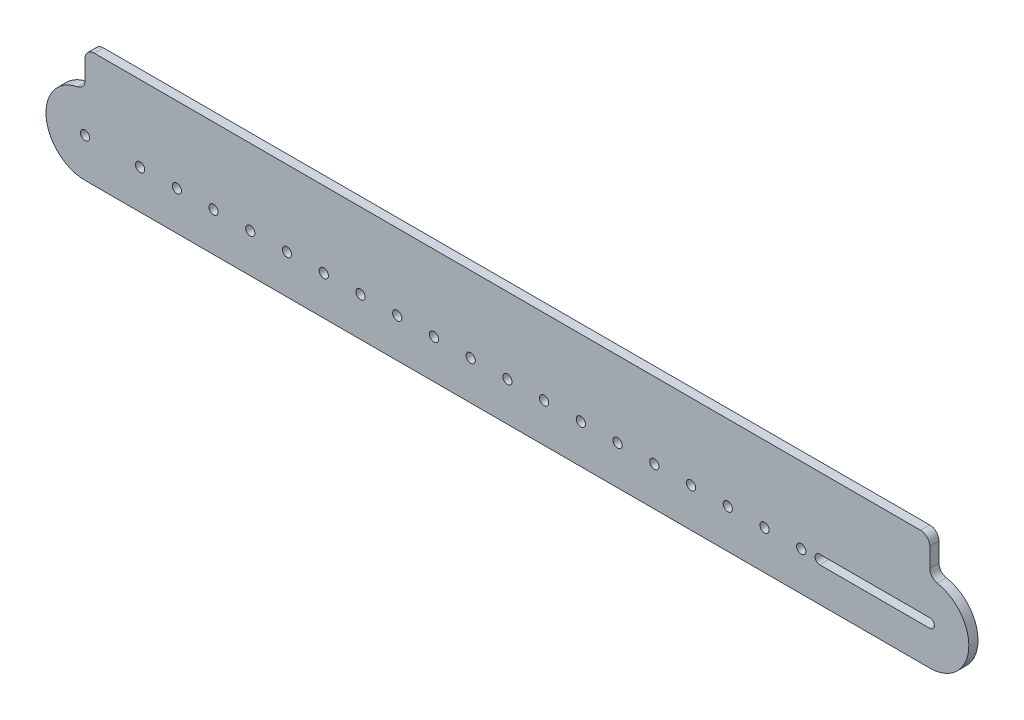
SolidWorks part; units mm, degrees
ref_plane "Front Plane" through (0, 0, 0) normal (0, 0, 1) x (1, 0, 0)
ref_plane "Top Plane" through (0, 0, 0) normal (0, 1, 0) x (1, 0, 0)
ref_plane "Right Plane" through (0, 0, 0) normal (1, 0, 0) x (0, 0, -1)
sketch "Sketch1" plane through (0, 0, 0) normal (0, 0, 1) x (1, 0, 0)
  line L0 (0, 26.9875) -> (584.2, 26.9875)
  line L1 (0, -26.9875) -> (584.2, -26.9875)
  line L2 (0, 26.9875) -> (584.2, 26.9875)
  line L3 (0, 26.9875) -> (0, 52.3875)
  line L4 (584.2, 26.9875) -> (584.2, 52.3875)
  line L5 (0, 52.3875) -> (584.2, 52.3875)
  arc A0 (0, 26.9875) -> (0, -26.9875) centre (0, 0) ccw
  arc A1 (584.2, -26.9875) -> (584.2, 26.9875) centre (584.2, 0) ccw
extrude "Boss-Extrude1" add sketch "Sketch1" along normal mid plane 6.35 contours L5 L3 L0 L4 | L1 A1 L0 A0 region at (292.1, 39.6875, 0) region at (292.1, 0, 0)
sketch "Sketch2" plane through (0, 0, 3.175) normal (0, 0, 1) x (1, 0, 0)
  line L3 (508, 3.175) -> (584.2, 3.175)
  line L4 (508, -3.175) -> (584.2, -3.175)
  arc A1 (584.2, -3.175) -> (584.2, 3.175) centre (584.2, 0) ccw
  arc A3 (508, 3.175) -> (508, -3.175) centre (508, 0) ccw
  circle A5 centre (0, 0) radius 3.175
  circle A6 centre (0, 0) radius 26.9875 construction
  circle A7 centre (38.1, 0) radius 3.175
  circle A8 centre (63.5, 0) radius 3.175
  circle A9 centre (88.9, 0) radius 3.175
  circle A10 centre (114.3, 0) radius 3.175
  circle A11 centre (139.7, 0) radius 3.175
  circle A12 centre (165.1, 0) radius 3.175
  circle A13 centre (190.5, 0) radius 3.175
  circle A14 centre (215.9, 0) radius 3.175
  circle A15 centre (241.3, 0) radius 3.175
  circle A16 centre (266.7, 0) radius 3.175
  circle A17 centre (292.1, 0) radius 3.175
  circle A18 centre (317.5, 0) radius 3.175
  circle A19 centre (342.9, 0) radius 3.175
  circle A20 centre (368.3, 0) radius 3.175
  circle A21 centre (393.7, 0) radius 3.175
  circle A22 centre (419.1, 0) radius 3.175
  circle A23 centre (444.5, 0) radius 3.175
  circle A24 centre (469.9, 0) radius 3.175
  circle A25 centre (495.3, 0) radius 3.175
  dimension "D1" = 38.1
  dimension "D2" = 19
extrude "Cut-Extrude1" cut sketch "Sketch2" against normal through all
fillet "Fillet1" radius 6.35 4 edges at (0, 26.9875, 0) (584.2, 26.9875, 0) (584.2, 52.3875, 0) (0, 52.3875, 0)
